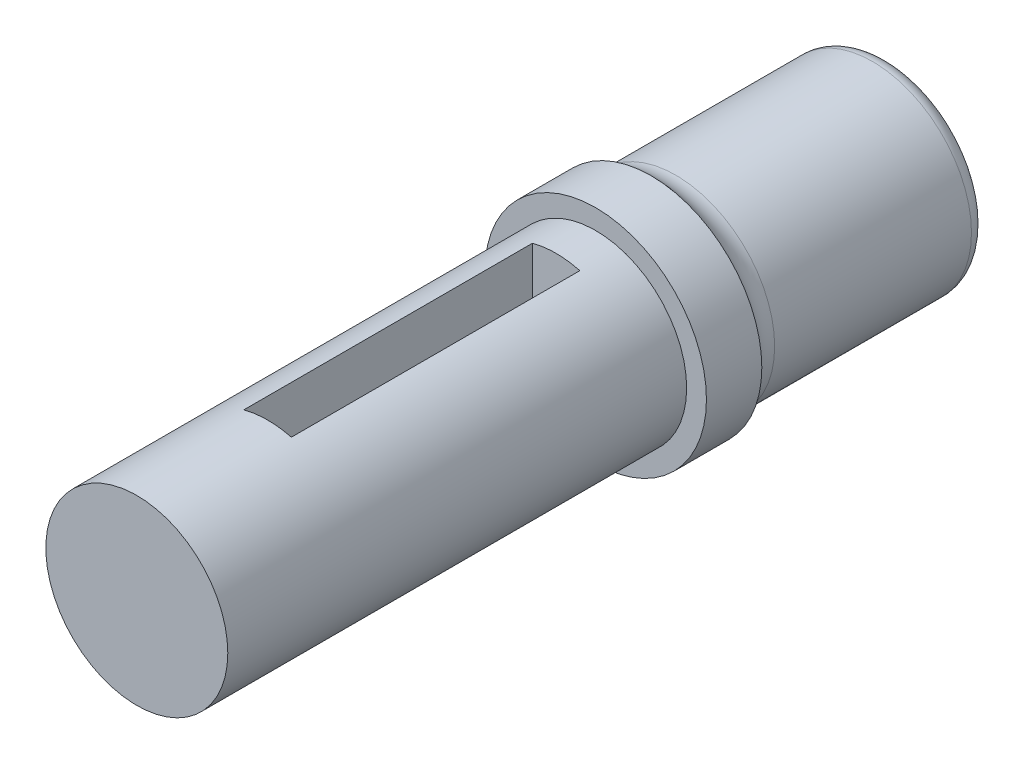
SolidWorks part; units mm, degrees
ref_plane "Front Plane" through (0, 0, 0) normal (0, 0, 1) x (1, 0, 0)
ref_plane "Top Plane" through (0, 0, 0) normal (0, 1, 0) x (1, 0, 0)
ref_plane "Right Plane" through (0, 0, 0) normal (1, 0, 0) x (0, 0, -1)
sketch "Sketch1" plane through (0, 0, 0) normal (0, 0, 1) x (1, 0, 0)
  circle A0 centre (0, 0) radius 70
  dimension "D1" = 140
extrude "Boss-Extrude1" add sketch "Sketch1" along normal blind 35
sketch "Sketch2" plane through (0, 0, 0) normal (0, 0, 1) x (1, 0, 0)
  circle A0 centre (0, 0) radius 62.5
  dimension "D1" = 125
extrude "Boss-Extrude2" add sketch "Sketch2" against normal blind 150
fillet "Fillet1" radius 20 1 edges at (62.5, 0, 0)
sketch "Sketch3" plane through (0, 0, 0) normal (0, 0, 1) x (1, 0, 0)
  circle A0 centre (0, 0) radius 57.5
  dimension "D1" = 115
extrude "Boss-Extrude3" add sketch "Sketch3" along normal blind 325
sketch "Sketch4" plane through (0, 0, 0) normal (1, 0, 0) x (0, 0, -1)
  line L4 (-240, 0) -> (-251.375, 273)
  line L5 (-251.375, 273) -> (-60, 273)
  line L6 (-60, 273) -> (-60, 0)
  line L7 (-60, -273) -> (-228.625, -273)
  line L8 (-228.625, -273) -> (-240, 0)
  line L9 (-60, -273) -> (-60, 0)
  dimension "D2" = 273
  dimension "D3" = 191.375
  dimension "D4" = 168.625
  dimension "D5" = 180
extrude "Cut-Extrude1" cut sketch "Sketch4" against normal blind 15 and the other way blind 15
fillet "Fillet2" radius 10 1 edges at (62.5, 0, -150)
